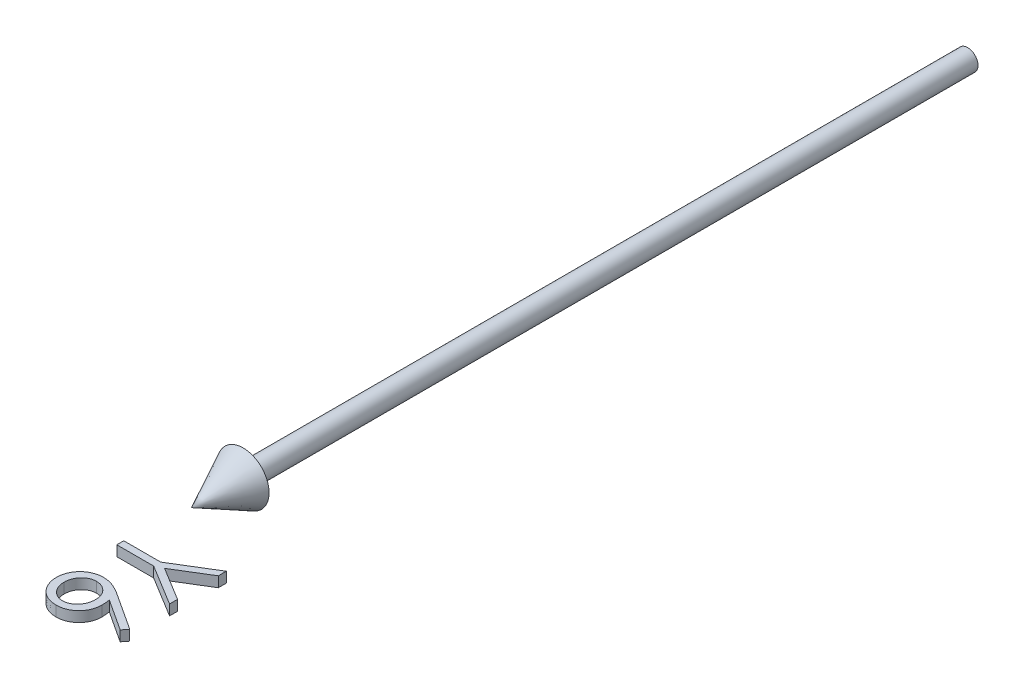
SolidWorks part; units mm, degrees
ref_plane "Front Plane" through (0, 0, 0) normal (0, 0, 1) x (1, 0, 0)
ref_plane "Top Plane" through (0, 0, 0) normal (0, 1, 0) x (1, 0, 0)
ref_plane "Right Plane" through (0, 0, 0) normal (1, 0, 0) x (0, 0, -1)
sketch "Sketch2" plane through (0, 0, 0) normal (0, 1, 0) x (1, 0, 0)
  line L0 (0, 41.95) -> (0, -114.4521) construction
  line L1 (-36.8894, 0) -> (41.4965, 0) construction
  line L2 (0, -150) -> (5, -140)
  line L3 (5, -140) -> (2, -140)
  line L4 (2, -140) -> (2, 0)
  line L5 (2, 0) -> (0, 0)
  line L6 (0, 0) -> (0, -150)
  dimension "D1" = 150
  dimension "D2" = 2
  dimension "D3" = 10
  dimension "D4" = 5
revolve "Revolve1" add sketch "Sketch2" angle 360 about L0
sketch "Sketch3" plane through (0, 0, 0) normal (0, 1, 0) x (1, 0, 0)
  line L0 (0, -157.5) -> (0, -224.9757) construction
  line L1 (-16.183, 0) -> (29.166, 0) construction
  text T0 "Y6\r\n\r\n\r\n" font "Century Gothic" height 15
  dimension "D1" = 157.5
extrude "Boss-Extrude1" add sketch "Sketch3" against normal blind 1 and the other way blind 1 separate body
equation "\"D1@Sketch2\"=\"frame_arrow_length\""
equation "\"D2@Sketch2\"=\"frame_arrow_odA\"/2"
equation "\"D4@Sketch2\"=\"frame_arrow_head_od\""
equation "\"D3@Sketch2\"=\"frame_arrow_head_length\""
equation "\"frame_arrow_length\"=150"
equation "\"frame_arrow_head_length\"=10"
equation "\"frame_arrow_head_od\"=5"
equation "\"frame_arrow_odA\"=4"
equation "\"D1@Sketch3\"=\"frame_arrow_length\"*1.05"
